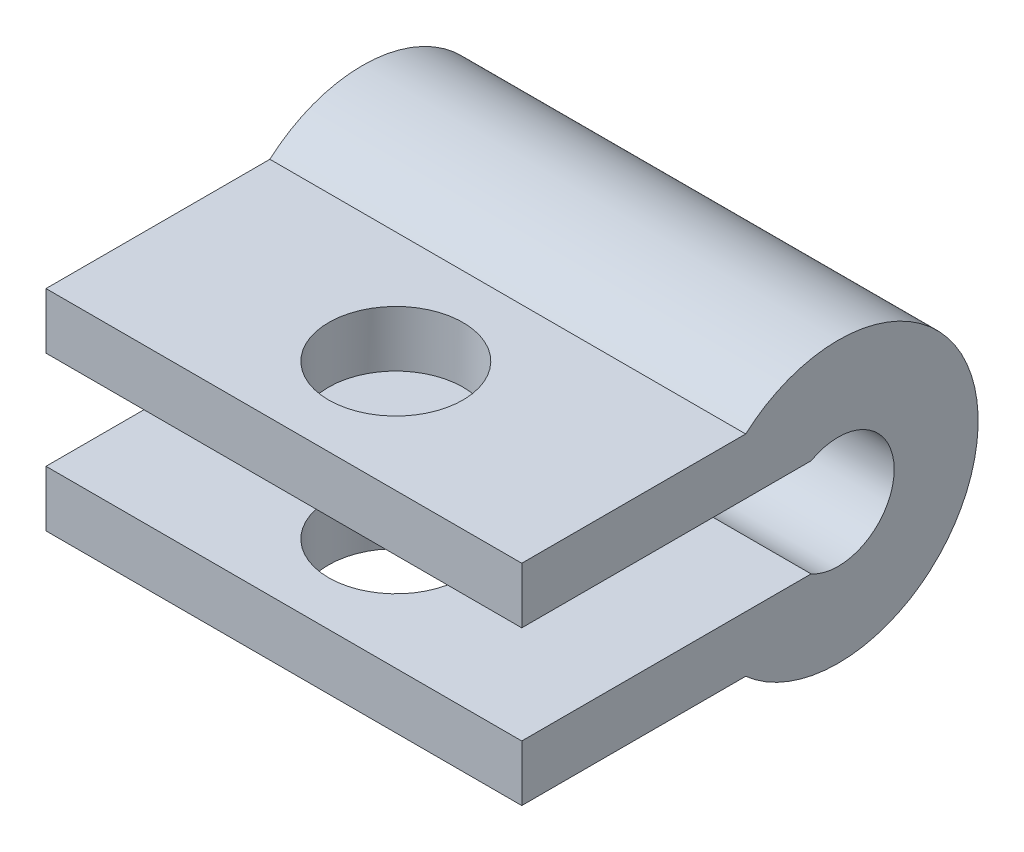
SolidWorks part; units mm, degrees
material "ABS"
ref_plane "Plan de face" through (0, 0, 0) normal (0, 0, 1) x (1, 0, 0)
ref_plane "Plan de dessus" through (0, 0, 0) normal (0, 1, 0) x (1, 0, 0)
ref_plane "Plan de droite" through (0, 0, 0) normal (1, 0, 0) x (0, 0, -1)
sketch "Esquisse1" plane through (0, 0, 0) normal (1, 0, 0) x (0, 0, -1)
  line L2 (-3.3072, 3.75) -> (-11.3072, 3.75)
  line L3 (-11.3072, 3.75) -> (-11.3072, 1.75)
  line L4 (-11.3072, 1.75) -> (-0.9682, 1.75)
  line L7 (-3.3072, -3.75) -> (-11.3072, -3.75)
  line L8 (-11.3072, -3.75) -> (-11.3072, -1.75)
  line L9 (-11.3072, -1.75) -> (-0.9682, -1.75)
  arc A0 (-3.3072, 3.75) -> (-3.3072, -3.75) centre (0, 0) cw
  arc A1 (-0.9682, 1.75) -> (-0.9682, -1.75) centre (0, 0) cw
  point P28 (-3.3072, 3.75)
  point P31 (-11.3072, 1.75)
  point P34 (-11.3072, -3.75)
  point P37 (-11.3072, -1.75)
  point P40 (-11.3072, 3.75)
  dimension "D1" = 5
  dimension "D2" = 2
  dimension "D3" = 2
  dimension "D4" = 2
  dimension "D5" = 3.5
  dimension "D6" = 1.75
  dimension "D8" = 8
extrude "Boss.-Extru.1" add sketch "Esquisse1" along normal blind 8.5 and the other way blind 8.5
hole_wizard "Dégagement M41" positions "Esquisse2" profile "Esquisse3" hole size "M4" standard "Ansi Metric" end condition through all
sketch "Esquisse2" plane through (0, 3.75, 0) normal (0, 1, 0) x (1, 0, 0)
  line L0 (-8.5, -3.3072) -> (8.5, -3.3072) construction
  point P0 (0, -7.3072)
  dimension "D1" = 4
sketch "Esquisse3" plane through (0, 3.75, 7.3072) normal (1, 0, 0) x (0, 0, 1)
  line L0 (0, 0) -> (0, 8.75)
  line L1 (0, 8.75) -> (2.4, 8.75)
  line L2 (2.4, 8.75) -> (2.4, 0)
  line L5 (2.4, 0) -> (0, 0)
  line L11 (0, -6.35) -> (0, 107.95) construction
  dimension "Diamètre du perçage jusqu'au prochain" = 4.8
  dimension "Profondeur du perçage jusqu'au prochain" = 8.75
